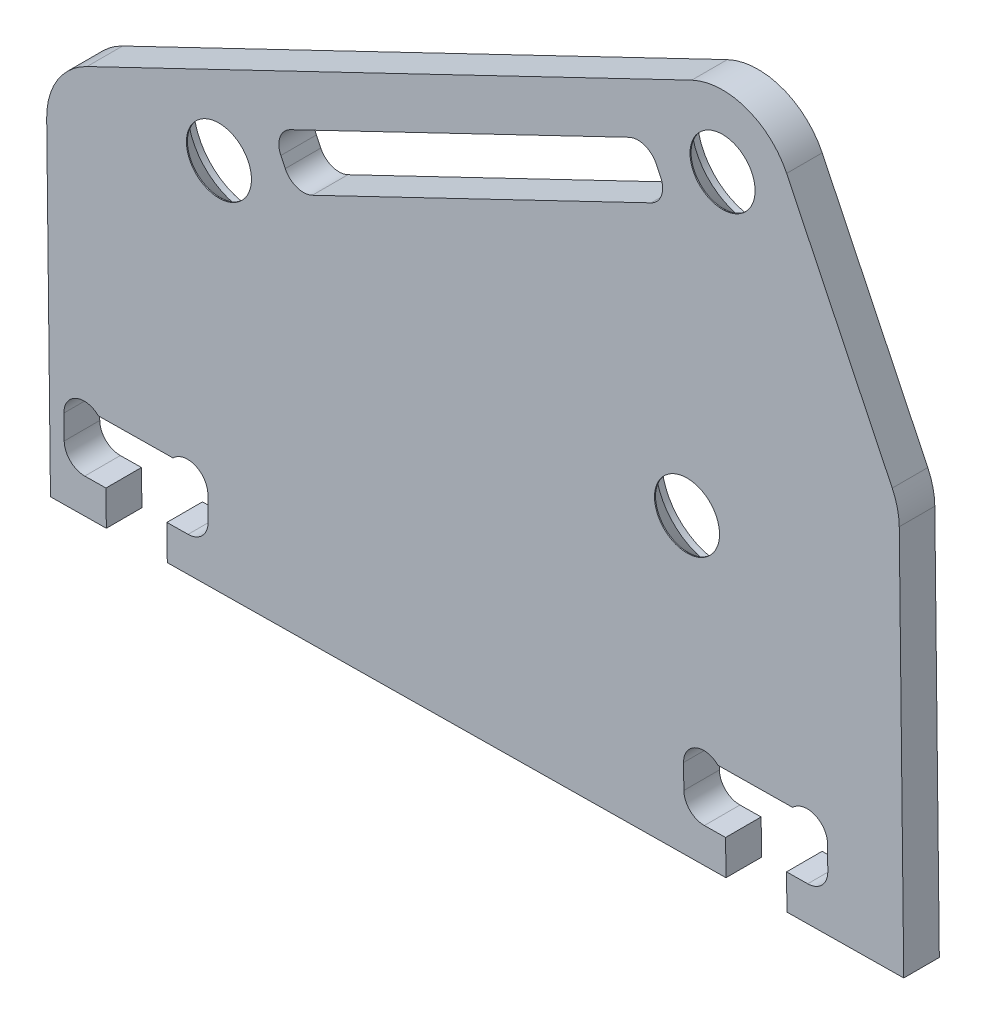
SolidWorks part; units mm, degrees
ref_plane "Front Plane" through (0, 0, 0) normal (0, 0, 1) x (1, 0, 0)
ref_plane "Top Plane" through (0, 0, 0) normal (0, 1, 0) x (1, 0, 0)
ref_plane "Right Plane" through (0, 0, 0) normal (1, 0, 0) x (0, 0, -1)
sketch "Sketch2" plane through (277.9441, -368.7823, 0) normal (0, 0, 1) x (0.9999, 0.0116, 0)
  line L0 (-273.6458, 371.9829) -> (-231.6458, 371.9829)
  line L1 (-237.0451, 403.462) -> (-231.9737, 392.5863)
  line L2 (-273.6458, 390.2567) -> (-231.6458, 390.2567) construction
  line L3 (-269.3958, 375.2829) -> (-238.8958, 375.2829) construction
  line L4 (-238.8958, 373.9829) -> (-238.8958, 371.9829) construction
  line L5 (-241.6964, 405.155) -> (-273.6458, 390.2567)
  line L6 (-273.6458, 390.2567) -> (-273.6458, 371.9829)
  line L7 (-242.1458, 376.5829) -> (-235.6458, 376.5829)
  line L8 (-265.1407, 390.3609) -> (-240.2172, 401.9829) construction
  line L9 (-260.534, 391.1298) -> (-243.7673, 398.9482)
  line L10 (-261.8629, 391.6135) -> (-262.0742, 392.0666)
  line L11 (-243.2836, 400.2771) -> (-243.4949, 400.7303)
  line L12 (-261.5905, 393.3955) -> (-244.8238, 401.214)
  line L13 (-261.4403, 390.7072) -> (-243.9175, 401.6366) construction
  line L14 (-270.1458, 388.0269) -> (-240.2172, 401.9829) construction
  line L15 (-242.861, 399.3708) -> (-262.4968, 392.9729) construction
  line L16 (-254.1458, 375.2829) -> (-254.1458, 371.9829) construction
  line L17 (-242.1458, 376.5829) -> (-242.1458, 373.9829)
  line L18 (-242.1458, 373.9829) -> (-235.6458, 373.9829)
  line L19 (-235.6458, 376.5829) -> (-235.6458, 373.9829)
  line L20 (-242.1458, 376.5829) -> (-235.6458, 373.9829) construction
  line L21 (-242.1458, 373.9829) -> (-235.6458, 376.5829) construction
  line L22 (-242.1458, 376.5829) -> (-239.5458, 373.9829) construction
  line L23 (-240.3958, 371.9829) -> (-237.3958, 371.9829)
  line L24 (-240.3958, 371.9829) -> (-240.3958, 373.9829)
  line L25 (-240.3958, 373.9829) -> (-237.3958, 373.9829)
  line L26 (-237.3958, 371.9829) -> (-237.3958, 373.9829)
  line L27 (-240.3958, 371.9829) -> (-237.3958, 373.9829) construction
  line L28 (-240.3958, 373.9829) -> (-237.3958, 371.9829) construction
  line L29 (-238.8958, 376.5829) -> (-238.8958, 373.9829) construction
  line L30 (-242.4387, 374.69) -> (-242.4387, 375.8758)
  line L31 (-235.3529, 375.8758) -> (-235.3529, 374.69)
  line L32 (-267.8958, 371.9829) -> (-267.8958, 373.9829)
  line L33 (-270.8958, 371.9829) -> (-270.8958, 373.9829)
  line L34 (-266.1458, 373.9829) -> (-272.6458, 373.9829)
  line L35 (-272.9387, 375.8758) -> (-272.9387, 374.69)
  line L36 (-266.1458, 376.5829) -> (-272.6458, 376.5829)
  line L37 (-265.8529, 374.69) -> (-265.8529, 375.8758)
  line L38 (-241.4387, 373.69) -> (-236.3529, 373.69)
  line L39 (-231.6458, 391.1072) -> (-231.6458, 371.9829)
  line L40 (-266.8529, 373.69) -> (-271.9387, 373.69)
  circle A0 centre (-242.1458, 386.4829) radius 1.6
  circle A1 centre (-265.1407, 390.3609) radius 1.6
  circle A2 centre (-240.2172, 401.9829) radius 1.6
  circle A3 centre (-270.1458, 388.0269) radius 3.5
  circle A4 centre (-240.2172, 401.9829) radius 3.5
  arc A5 (-262.0742, 392.0666) -> (-261.5905, 393.3955) centre (-261.1679, 392.4892) cw
  circle A6 centre (-235.1458, 391.1072) radius 3.5
  circle A7 centre (-241.4387, 375.8758) radius 1
  circle A8 centre (-236.3529, 375.8758) radius 1
  circle A9 centre (-236.3529, 374.69) radius 1
  circle A10 centre (-241.4387, 374.69) radius 1
  arc A11 (-261.8629, 391.6135) -> (-260.534, 391.1298) centre (-260.9566, 392.0361) ccw
  arc A12 (-243.7673, 398.9482) -> (-243.2836, 400.2771) centre (-244.1899, 399.8545) ccw
  circle A13 centre (-271.9387, 374.69) radius 1
  circle A14 centre (-271.9387, 375.8758) radius 1
  circle A15 centre (-266.8529, 375.8758) radius 1
  circle A16 centre (-266.8529, 374.69) radius 1
  arc A17 (-243.4949, 400.7303) -> (-244.8238, 401.214) centre (-244.4012, 400.3077) ccw
  spline S0 degree 3 poles (-273.6458, 390.2567) (-280.963, 386.8446) (-277.7104, 371.9829) (-273.6458, 371.9829) knots 0 0 0 0 1 1 1 1
  point P10 (-252.6789, 396.1719)
  point P15 (-240.2172, 401.9829)
  point P21 (-238.8958, 372.9829)
  dimension "D1" = 3.2
  dimension "D10" = 3
  dimension "D13" = 20.5
  dimension "D2" = 7
  dimension "D17" = 1
  dimension "D11" = 45
  dimension "D14" = 2
  dimension "D3" = 30
  dimension "D4" = 12
  dimension "D5" = 30.5
  dimension "D6" = 4.25
  dimension "D7" = 6.5
  dimension "D8" = 2.6
  dimension "D9" = 2
  dimension "D12" = 2.5
  dimension "D15" = 25
  dimension "D16" = 14.5
  dimension "D18" = 12
  dimension "D19" = 42
extrude "Boss-Extrude1" add sketch "Sketch2" along normal blind 1.75 contours A17 L11 A4 L5 A3 L6 L0 L39 A6 L1 A12 L9 A11 L10 A5 L12 A1 A0 | A3 | A6 | A4 A2 region at (22.3525, 12.8403, 0) region at (3.3136, 16.0836, 0) region at (34.2042, 33.5951, 0) region at (38.2755, 19.5698, 0)
sketch "Sketch3" plane through (0, 0, 1.75) normal (0, 0, 1) x (1, 0, 0)
  circle A0 centre (8.2913, 18.4755) radius 3
  circle A1 centre (31.3296, 14.8646) radius 3
  circle A2 centre (33.0782, 30.3859) radius 3
  dimension "D1" = 6
extrude "Cut-Extrude2" [suppressed] cut sketch "Sketch3" against normal blind 0.3
chamfer "Chamfer1" [suppressed] distance 1.4 angle 45
sketch "Sketch4" plane through (0, 0, 0) normal (0, 0, -1) x (-1, 0, 0)
  circle A0 centre (-33.0782, 30.3859) radius 3
  circle A1 centre (-8.2913, 18.4755) radius 3
  circle A2 centre (-31.3296, 14.8646) radius 3
  dimension "D1" = 6
extrude "Cut-Extrude3" cut sketch "Sketch4" against normal blind 0.3
chamfer "Chamfer2" distance 1.4 angle 45 3 edges at (29.7296, 14.8646, 0.3) (6.6913, 18.4755, 0.3) (31.4782, 30.3859, 0.3)
